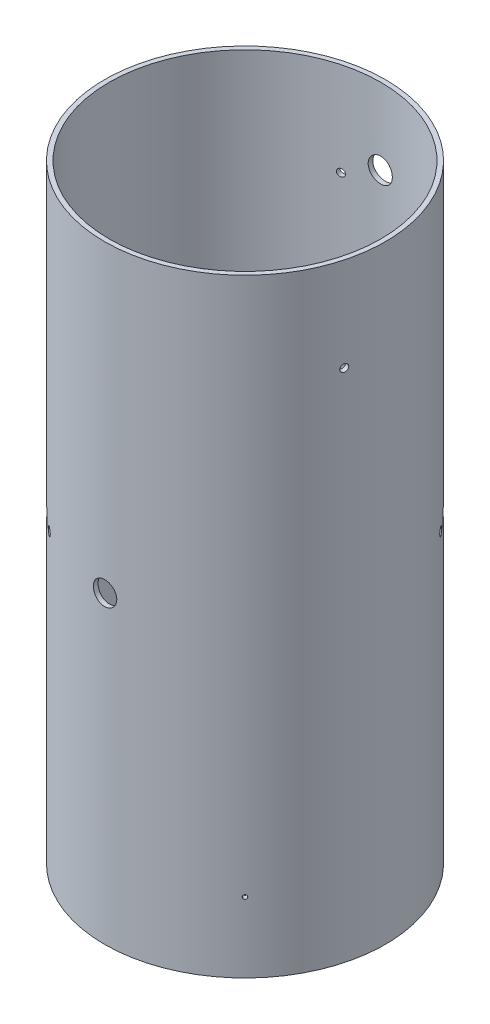
SolidWorks part; units mm, degrees
material "A-Glass Fiber"
ref_plane "Front Plane" through (0, 0, 0) normal (0, 0, 1) x (1, 0, 0)
ref_plane "Top Plane" through (0, 0, 0) normal (0, 1, 0) x (1, 0, 0)
ref_plane "Right Plane" through (0, 0, 0) normal (1, 0, 0) x (0, 0, -1)
sketch "Sketch1" plane through (0, 0, 0) normal (0, 1, 0) x (1, 0, 0)
  circle A0 centre (0, 0) radius 76.1746
  circle A1 centre (0, 0) radius 73.66
  dimension "D1" = 152.3492
  dimension "D2" = 147.32
extrude "Boss-Extrude1" add sketch "Sketch1" along normal blind 330.2
sketch "Sketch4" plane through (0, 0, 0) normal (0, 0, 1) x (1, 0, 0)
  line L0 (-76.1746, 0) -> (76.1746, 0) construction
  line L1 (76.1746, 330.2) -> (-76.1746, 330.2) construction
  line L2 (0, 330.2) -> (0, 0) construction
  line L3 (73.66, 330.2) -> (-73.66, 330.2) construction
  point P0 (0, 41.275)
  point P3 (0, 288.925)
  dimension "D1" = 41.275
  dimension "D2" = 41.275
hole_wizard "1/2 Clearance Hole5" positions "Sketch16" profile "Sketch17" hole size "1/2" standard "ANSI Inch"
sketch "Sketch16" plane through (0, 0, 0) normal (0, 0, 1) x (1, 0, 0)
  point P0 (0, 288.925)
sketch "Sketch17" plane through (0, 288.925, 0) normal (1, 0, 0) x (0, -1, 0)
  line L0 (0, 0) -> (0, 80.1345)
  line L1 (0, 80.1345) -> (6.5481, 76.2)
  line L2 (6.5481, 76.2) -> (6.5481, 0)
  line L5 (6.5481, 0) -> (0, 0)
  line L10 (0, 80.1345) -> (-6.5481, 76.2) construction
  line L11 (0, -6.35) -> (0, 107.95) construction
  dimension "Hole Dia." = 13.0962
  dimension "Hole Depth" = 76.2
  dimension "Drill Angle" = 118
sketch "Sketch27" plane through (0, 0, 0) normal (0, 0, 1) x (1, 0, 0)
  line L0 (0, 330.2) -> (0, 0) construction
  line L1 (-76.1746, 0) -> (76.1746, 0) construction
  circle A0 centre (0, 165.1) radius 6.35
  dimension "D1" = 12.7
  dimension "D2" = 165.1
extrude "Cut-Extrude1" cut sketch "Sketch27" against normal through all both and the other way through all
ref_plane "Plane1" through (0, 0, 0) normal (-0.7071, 0, 0.7071) x (0.7071, 0, 0.7071)
ref_plane "Plane2" through (0, 0, 0) normal (-0.7071, 0, 0.7071) x (0, -1, 0)
sketch "Sketch30" plane through (0, 0, 0) normal (-0.7071, 0, 0.7071) x (0.7071, 0, 0.7071)
  line L0 (0, 330.2) -> (0, 0) construction
  line L1 (4.953, 160.147) -> (-4.953, 160.147)
  line L2 (4.953, 160.147) -> (4.953, 170.053)
  line L3 (4.953, 170.053) -> (-4.953, 170.053)
  line L4 (-4.953, 160.147) -> (-4.953, 170.053)
  line L5 (4.953, 160.147) -> (-4.953, 170.053) construction
  line L6 (4.953, 170.053) -> (-4.953, 160.147) construction
  line L7 (-76.1746, 0) -> (76.1746, 0) construction
  circle A0 centre (-12.7, 165.1) radius 2.1831
  circle A1 centre (12.7, 165.1) radius 2.1831
  point P0 (0, 165.1)
  dimension "D3" = 4.3663
  dimension "D4" = 4.3663
  dimension "D1" = 9.906
  dimension "D2" = 9.906
  dimension "D5" = 12.7
  dimension "D6" = 12.7
  dimension "D7" = 165.1
extrude "Cut-Extrude2" cut sketch "Sketch30" against normal through all both and the other way through all
sketch "Sketch23" plane through (0, 0, 0) normal (-0.7071, 0, 0.7071) x (0.7071, 0, 0.7071)
  line L0 (0, 0) -> (0, 330.2) construction
  line L1 (73.66, 330.2) -> (-73.66, 330.2) construction
  line L2 (-76.1746, 165.1) -> (76.1746, 165.1) construction
  line L3 (76.1746, 0) -> (76.1746, 330.2) construction
  circle A1 centre (0, 38.1) radius 1.0922
  point P12 (0, 165.1)
  dimension "D2" = 127
extrude "Shear Scrrews" cut sketch "Sketch23" against normal through all
pattern_circular "CirPattern1" count 4 over 360 about axis through (0, 330.2, 0) along (0, -1, 0) of "Shear Scrrews"
hole_wizard "Ø4.0 (4) Diameter Hole1" positions "Sketch24" profile "Sketch25" hole size "Ø4.0" standard "ANSI Metric"
sketch "Sketch24" plane through (0, 0, 0) normal (-0.7071, 0, 0.7071) x (0, -1, 0)
  line L0 (-330.2, 76.1746) -> (-330.2, -76.1746) construction
  point P0 (-279.4, 0)
  dimension "D1" = 50.8
sketch "Sketch25" plane through (0, 279.4, 0) normal (0, 1, 0) x (-0.7071, 0, -0.7071)
  line L0 (0, 0) -> (0, 90.1017)
  line L1 (0, 90.1017) -> (2, 88.9)
  line L2 (2, 88.9) -> (2, 0)
  line L5 (2, 0) -> (0, 0)
  line L10 (0, 90.1017) -> (-2, 88.9) construction
  line L11 (0, -6.35) -> (0, 107.95) construction
  dimension "Hole Dia." = 4
  dimension "Hole Depth" = 88.9
  dimension "Drill Angle" = 118
pattern_circular "CirPattern2" count 3 over 360 about axis through (0, 330.2, 0) along (0, 1, 0) of "Ø4.0 (4) Diameter Hole1"
equation "\"Mid_Coupler_Length\" = 13in"
equation "\"D1@Boss-Extrude1\"=\"Mid_Coupler_Length\""
equation "\"Shear_Screw_Coupler_Location\" = 4.5in"
equation "\"Shear_Screw_Diameter\" = 0.086in"
equation "\"D2@Sketch23\"=\"Shear_Screw_Coupler_Location\"+0.5"
equation "\"Mid_Tube_Length\"= 1in"
equation "\"Bodytube_OD\" = 6.17in"
equation "\"Bodytube_ID\" = 5.998in"
equation "\"Camera_Cutout_Width\"=10mm"
equation "\"Camera_Cutout_Height\"=7mm"
equation "\"Fwd_Tube_Length\" = 38.5in"
equation "\"BKHD_Screw_Diam\"= 3.5mm"
equation "\"Fwd_BKHD_From_Top\" = 18in"
equation "\"Motor_OD\" = 4in"
equation "\"Aft_Section_Length\"= 36in"
equation "\"AB_Coupler_OD_Length\"= 1in"
equation "\"AB_Coupling_Section_Length\"= 0.375in"
equation "\"AB_Coupler_Length\"= \"AB_Coupler_OD_Length\" + \"AB_Coupling_Section_Length\" * 2"
equation "\"Cutout_Angle\" = 80"
equation "\"AB_Paddle_Height\" = 0.375in"
equation "\"AB_Coupler_Num_Screws\"= 4"
equation "\"AB_BKHD_Thickness\" = 0.375in"
equation "\"AB_Mount_From_Bottom\" = 23.175in"
equation "\"Num_Cutouts\" = 3"
equation "\"AB_Coupler_OD\"= 6.17in"
equation "\"AB_Coupler_ID\"= 5.75in"
equation "\"AB_Coupler_Surface_Diameter\"= 5.998in"
equation "\"AB_Coupling_Screw_Diameter\"= 0.15748in"
equation "\"AB_Central_Bushing_Length\" = .4724in"
equation "\"Lead_Screw_Dist\" = 3.4in"
equation "\"Lead_Screw_Diam\" = 0.386in"
equation "\"Lead_Screw_Length\" = (\"Mid_Coupler_Length\" + 2*0.375in + 2*.75in)"
equation "\"Paddle_Pin_Offset\" = .25in"
equation "\"Paddle_Pin_Radius\" = 2.25in"
equation "\"SS_Paddle_Pin_Radius\" = 2.25*0.66in"
equation "\"Paddle_Gear_OD\" = 3.2in"
equation "\"Drive_Gear_OD\" = 1.7in"
equation "\"Fin_Thickness\"= .118in"
equation "\"Guiderail_Cutout_Diameter\"= 1.5in"
equation "\"DB9_Hole_Dist\" = 25mm"
equation "\"DB9_Relief_Width\" = 0.47in"
equation "\"DB9_Relief_Hole_Offset\" = 0.09in"
equation "\"Airbrakes_Wire_Hole_Dia\" = .25in"
equation "\"Airbrakes_Wire_Hole_Dist\" = 1.1in"
equation "\"Servo_Gear_Offset\" = 0.5in"
equation "\"FWD_Shear_Screw_Dist\" = 1.5in"
equation "\"Camera_Screw_Dia\" = 0.216535"
equation "\"Camera_Hole_Angle\" = atn ( 2 / 3 * tan ( 12.5deg ) )"
equation "\"D2\" = \"Camera_Hole_Angle\""
equation "\"Coupler_OD\" = 5.998"
equation "\"D1@Sketch1\"=\"Coupler_OD\""
equation "\"Coupler_ID\" = 5.8"
equation "\"D2@Sketch1\"=\"Coupler_ID\""
